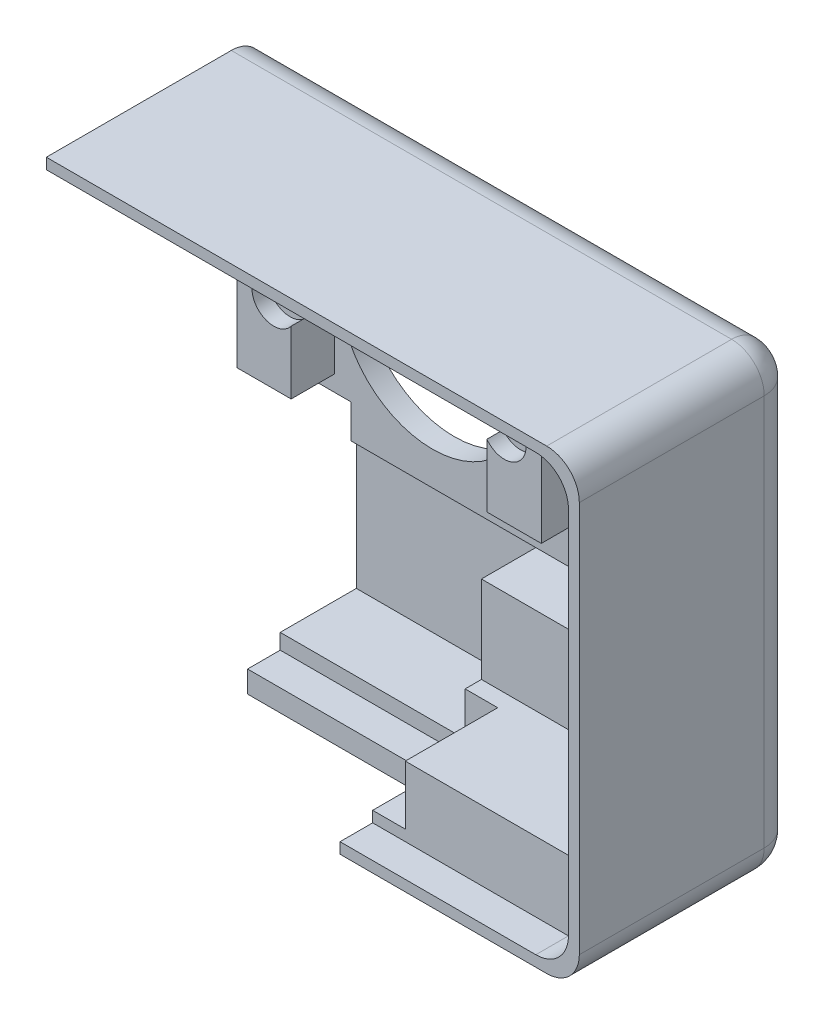
SolidWorks part; units mm, degrees
material "ABS"
ref_plane "Front Plane" through (0, 0, 0) normal (0, 0, 1) x (1, 0, 0)
ref_plane "Top Plane" through (0, 0, 0) normal (0, 1, 0) x (1, 0, 0)
ref_plane "Right Plane" through (0, 0, 0) normal (1, 0, 0) x (0, 0, -1)
sketch "Sketch1" plane through (0, 0, 0) normal (0, 0, 1) x (1, 0, 0)
  line L1 (-31, 21) -> (31, 21)
  line L2 (-31, 21) -> (-31, -21)
  line L3 (-31, -21) -> (31, -21)
  line L4 (31, 21) -> (31, -21)
  line L5 (-31, 21) -> (31, -21) construction
  line L6 (-31, -21) -> (31, 21) construction
  point P0 (0, 0)
  dimension "D1" = 42
  dimension "D2" = 62
extrude "Boss-Extrude1" add sketch "Sketch1" along normal blind 20 contours L4 L3 L2 L1
sketch "Sketch8" plane through (0, 0, 20) normal (0, 0, 1) x (1, 0, 0)
  line L0 (-31, 21) -> (31, 21) construction
  line L1 (-12, 19) -> (12, 19)
  line L2 (-12, 19) -> (-12, -19)
  line L3 (-12, -19) -> (12, -19)
  line L4 (12, 19) -> (12, -19)
  line L5 (-12, 19) -> (12, -19) construction
  line L6 (-12, -19) -> (12, 19) construction
  point P0 (0, 0)
  dimension "D1" = 24
  dimension "D2" = 38
  dimension "D3" = 2
  dimension "D4" = 2
extrude "Cut-Extrude1" cut sketch "Sketch8" against normal blind 11.5
sketch "Sketch9" plane through (0, 0, 8.5) normal (0, 0, 1) x (1, 0, 0)
  line L1 (12, 19) -> (-12, 19) construction
  circle A0 centre (-0.4945, 6) radius 8.5
  point P6 (-0.4945, 6)
  point P8 (-0.4945, 6)
  dimension "D1" = 17
  dimension "D2" = 13
extrude "Cut-Extrude2" cut sketch "Sketch9" against normal up to next
sketch "Sketch10" plane through (0, 0, 20) normal (0, 0, 1) x (1, 0, 0)
  line L0 (12, 19) -> (-12, 19) construction
  line L1 (-28.5, 17.583) -> (28.5, 17.583)
  line L2 (-28.5, 17.583) -> (-28.5, -5.583)
  line L3 (-28.5, -5.583) -> (28.5, -5.583)
  line L4 (28.5, 17.583) -> (28.5, -5.583)
  line L5 (-28.5, 17.583) -> (28.5, -5.583) construction
  line L6 (-28.5, -5.583) -> (28.5, 17.583) construction
  line L7 (12, 19) -> (-12, 19) construction
  point P0 (0, 6)
  point P5 (0, 17.583)
  point P6 (28.5, 6)
  point P13 (0, 19)
  dimension "D1" = 13
  dimension "D2" = 57
extrude "Cut-Extrude3" cut sketch "Sketch10" against normal blind 18
fillet "Fillet1" radius 3 4 edges at (31, 0, 0) (0, -21, 0) (-31, 0, 0) (0, 21, 0)
fillet "Fillet2" radius 3 8 edges at (30.1213, 20.1213, 0.8787) (30.1213, -20.1213, 0.8787) (-30.1213, -20.1213, 0.8787) (-30.1213, 20.1213, 0.8787) (31, 21, 11.5) (31, -21, 11.5) (-31, -21, 11.5) (-31, 21, 11.5)
sketch "Sketch11" plane through (0, 0, 20) normal (0, 0, 1) x (1, 0, 0)
  line L1 (-9, -13) -> (9, -13)
  line L2 (-9, -13) -> (-9, -21)
  line L3 (-9, -21) -> (9, -21)
  line L4 (9, -13) -> (9, -21)
  line L5 (-28, -21) -> (28, -21) construction
  dimension "D1" = 18
  dimension "D2" = 8
extrude "Cut-Extrude4" cut sketch "Sketch11" against normal blind 8.5
sketch "Sketch12" plane through (0, 0, 20) normal (0, 0, 1) x (1, 0, 0)
  line L1 (-30, 20) -> (30, 20)
  line L2 (-30, 20) -> (-30, -20)
  line L3 (-30, -20) -> (30, -20)
  line L4 (30, 20) -> (30, -20)
  line L7 (-9, -21) -> (9, -21) construction
  line L8 (31, 18) -> (31, -18) construction
  point P4 (0, -20)
  point P9 (0, -21)
  point P10 (30, 0)
  point P13 (31, 0)
  dimension "D1" = 60
  dimension "D2" = 40
extrude "Cut-Extrude5" cut sketch "Sketch12" against normal blind 3
fillet "Fillet3" radius 3 4 edges at (-30, -20, 18.5) (30, -20, 18.5) (30, 20, 18.5) (-30, 20, 18.5)
sketch "Sketch13" plane through (0, 0, 8.5) normal (0, 0, 1) x (1, 0, 0)
  line L0 (-28.5, -5.583) -> (28.5, -5.583) construction
  line L1 (-9, -5.583) -> (9, -5.583)
  line L2 (-9, -5.583) -> (-9, -17.583)
  line L3 (-9, -17.583) -> (9, -17.583)
  line L4 (9, -5.583) -> (9, -17.583)
  line L5 (-9, -21) -> (9, -21) construction
  point P6 (0, -17.583)
  point P9 (0, -21)
  dimension "D1" = 12
  dimension "D2" = 18
extrude "Cut-Extrude6" cut sketch "Sketch13" against normal blind 7 contours L3 L4 L1 L2
sketch "Sketch18" plane through (0, 0, 0) normal (0, 0, -1) x (-1, 0, 0)
  line L1 (-25.0055, 9.5) -> (-14.5055, 9.5)
  line L2 (-25.0055, 9.5) -> (-25.0055, 2.5)
  line L3 (-25.0055, 2.5) -> (-14.5055, 2.5)
  line L4 (-14.5055, 9.5) -> (-14.5055, 2.5)
  line L5 (15.4945, 9.5) -> (25.9945, 9.5)
  line L6 (15.4945, 9.5) -> (15.4945, 2.5)
  line L7 (15.4945, 2.5) -> (25.9945, 2.5)
  line L8 (25.9945, 9.5) -> (25.9945, 2.5)
  point P8 (0.4945, 6)
  point P9 (-11.538, -9.5741)
  point P11 (-14.5055, 6)
  point P12 (0.4945, 5.1715)
  point P13 (-14.5055, 6)
  point P16 (15.4945, 6)
  dimension "D1" = 10.5
  dimension "D2" = 7
  dimension "D3" = 10.5
  dimension "D4" = 7
  dimension "D5" = 15
  dimension "D6" = 15
extrude "Cut-Extrude10" cut sketch "Sketch18" against normal up to next
sketch "Sketch22" plane through (0, 0, 2) normal (0, 0, 1) x (1, 0, 0)
  line L1 (-14.4945, 13) -> (-9.4945, 13)
  line L2 (-14.4945, 13) -> (-14.4945, -1)
  line L3 (-14.4945, -1) -> (-9.4945, -1)
  line L4 (-9.4945, 13) -> (-9.4945, -1)
  line L5 (8.5055, 13) -> (13.5055, 13)
  line L6 (8.5055, 13) -> (8.5055, -1)
  line L7 (8.5055, -1) -> (13.5055, -1)
  line L8 (13.5055, 13) -> (13.5055, -1)
  point P4 (-0.4945, 6)
  point P5 (-9.4945, 6)
  point P11 (0, 0)
  point P12 (8.5055, 6)
  point P13 (0, 0)
  dimension "D1" = 14
  dimension "D2" = 5
  dimension "D3" = 9
  dimension "D4" = 5
  dimension "D5" = 14
  dimension "D6" = 9
extrude "Boss-Extrude2" add sketch "Sketch22" along normal blind 4
sketch "Sketch16" plane through (0, 0, 6) normal (0, 0, 1) x (1, 0, 0)
  line L0 (-8.9945, 6) -> (8.1055, 6) construction
  line L1 (-0.4945, 14.5) -> (-0.4945, -2.5) construction
  circle A0 centre (-11.0945, 6) radius 2
  circle A1 centre (10.1055, 6) radius 2
  circle A2 centre (-0.4945, 6) radius 8.5 construction
  point P8 (-0.4945, 6)
  dimension "D1" = 4
  dimension "D2" = 10.6
  dimension "D4" = 4
  dimension "D3" = 10.6
extrude "Cut-Extrude9" cut sketch "Sketch16" against normal blind 1.5
chamfer "Chamfer1" distance 1 angle 45 8 edges at (-15.4945, 6, 0) (-20.7445, 2.5, 0) (-25.9945, 6, 0) (-20.7445, 9.5, 0) (19.7555, 2.5, 0) (14.5055, 6, 0) (19.7555, 9.5, 0) (25.0055, 6, 0)
sketch "Sketch19" plane through (0, 0, 17) normal (0, 0, 1) x (1, 0, 0)
  line L1 (-16.9659, 19.5) -> (17.0341, 19.5)
  line L2 (-16.9659, 19.5) -> (-16.9659, 18.3)
  line L3 (-16.9659, 18.3) -> (17.0341, 18.3)
  line L4 (17.0341, 19.5) -> (17.0341, 18.3)
  line L13 (27, 20) -> (-27, 20) construction
  dimension "D1" = 34
  dimension "D2" = 1.2
  dimension "D3" = 0.5
extrude "Cut-Extrude11" cut sketch "Sketch19" against normal blind 16
sketch "Sketch20" plane through (0, 0, 17) normal (0, 0, 1) x (1, 0, 0)
  line L0 (28.5, 17.583) -> (-28.5, 17.583) construction
  line L1 (-16.9659, 18.3) -> (17.0341, 18.3)
  line L2 (-16.9659, 18.3) -> (-16.9659, 17.583)
  line L3 (-16.9659, 17.583) -> (17.0341, 17.583)
  line L4 (17.0341, 18.3) -> (17.0341, 17.583)
  point P7 (0, 0)
  dimension "D1" = 34
extrude "Cut-Extrude12" cut sketch "Sketch20" against normal blind 10
sketch "Sketch23" plane through (0, 0, 7) normal (0, 0, 1) x (1, 0, 0)
  line L0 (28.5, 17.583) -> (-28.5, 17.583) construction
  line L1 (-16.9659, 18.3) -> (-4.9659, 18.3)
  line L2 (-16.9659, 18.3) -> (-16.9659, 17.583)
  line L3 (-16.9659, 17.583) -> (-4.9659, 17.583)
  line L4 (-4.9659, 18.3) -> (-4.9659, 17.583)
  dimension "D1" = 12
sketch "Sketch21" plane through (0, 0, 17) normal (0, 0, 1) x (1, 0, 0)
  line L0 (-28.5, -5.583) -> (-9, -5.583) construction
  line L1 (-30, -5.583) -> (30, -5.583)
  line L2 (-30, -5.583) -> (-30, -13.583)
  line L3 (-30, -13.583) -> (30, -13.583)
  line L4 (30, -5.583) -> (30, -13.583)
  line L6 (-9, -17.583) -> (9, -17.583) construction
  point P6 (0, -5.583)
  point P11 (0, -17.583)
  dimension "D1" = 60
  dimension "D2" = 8
extrude "Cut-Extrude13" cut sketch "Sketch21" against normal blind 10
sketch "Sketch14" plane through (-31, 0, 0) normal (-1, 0, 0) x (0, 0, 1)
  line L1 (-1.7152, 21.6241) -> (22.2862, 21.6241)
  line L2 (-1.7152, 21.6241) -> (-1.7152, -22.4964)
  line L3 (-1.7152, -22.4964) -> (22.2862, -22.4964)
  line L4 (22.2862, 21.6241) -> (22.2862, -22.4964)
extrude "Cut-Extrude7" cut sketch "Sketch14" against normal blind 13
sketch "Sketch15" plane through (-18, 0, 0) normal (-1, 0, 0) x (0, 0, 1)
  line L1 (-2.1743, -2.4792) -> (23.4683, -2.4792)
  line L2 (-2.1743, -2.4792) -> (-2.1743, -21.7159)
  line L3 (-2.1743, -21.7159) -> (23.4683, -21.7159)
  line L4 (23.4683, -2.4792) -> (23.4683, -21.7159)
extrude "Cut-Extrude8" cut sketch "Sketch15" against normal blind 10
extrude "Cut-Extrude14" cut sketch "Sketch23" against normal blind 5
